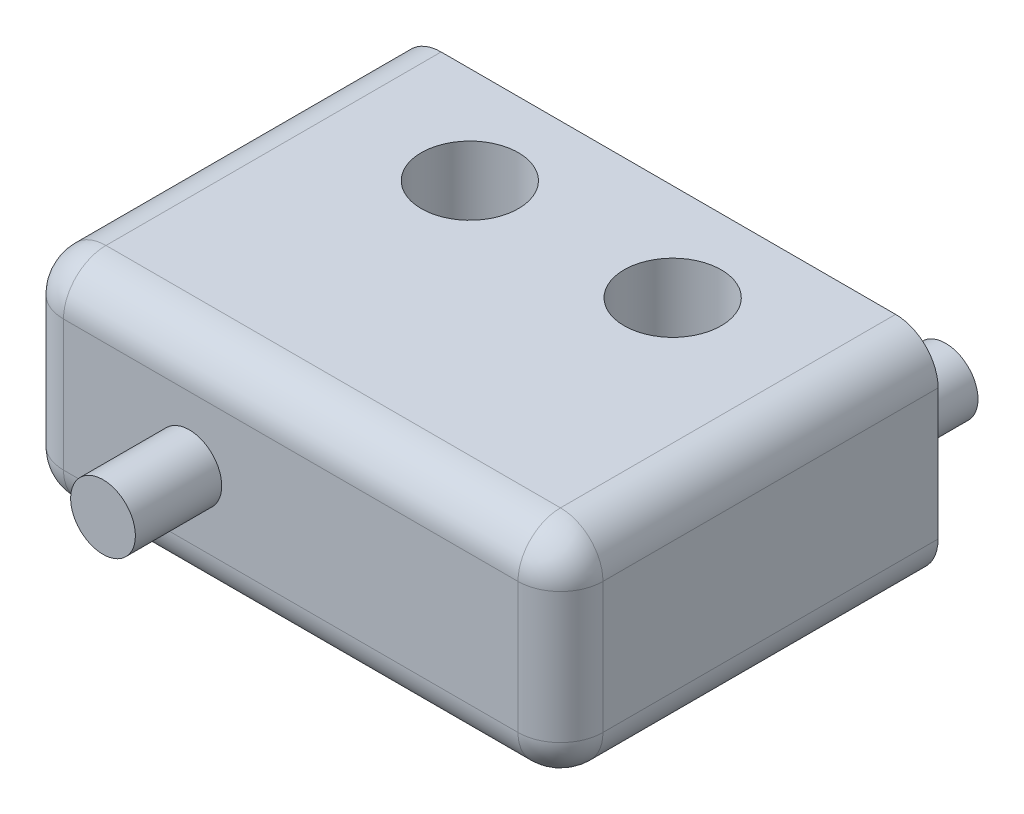
SolidWorks part; units mm, degrees
material "Калифорния"
ref_plane "Front" through (0, 0, 0) normal (0, 0, 1) x (1, 0, 0)
ref_plane "Top" through (0, 0, 0) normal (0, 1, 0) x (1, 0, 0)
ref_plane "Right" through (0, 0, 0) normal (1, 0, 0) x (0, 0, -1)
sketch "Эскиз1" plane through (0, 0, 0) normal (0, 0, 1) x (1, 0, 0)
  line L1 (-6.35, 2.54) -> (6.35, 2.54)
  line L2 (-6.35, 2.54) -> (-6.35, -2.54)
  line L3 (-6.35, -2.54) -> (6.35, -2.54)
  line L4 (6.35, 2.54) -> (6.35, -2.54)
  line L5 (-6.35, 2.54) -> (6.35, -2.54) construction
  line L6 (-6.35, -2.54) -> (6.35, 2.54) construction
  point P0 (0, 0)
  dimension "D1" = 12.7
  dimension "D2" = 5.08
extrude "Бобышка-Вытянуть1" add sketch "Эскиз1" along normal blind 8.89
sketch "Эскиз2" plane through (0, 0, 0) normal (0, 0, -1) x (-1, 0, 0)
  line L0 (6.35, 2.54) -> (6.35, -2.54) construction
  line L1 (-6.35, 2.54) -> (6.35, 2.54) construction
  circle A0 centre (-4.7498, 0) radius 0.762
  circle A1 centre (0, 0) radius 0.762
  circle A2 centre (4.7498, 0) radius 0.762
  dimension "D1" = 4.7498
  dimension "D2" = 4.7498
  dimension "D3" = 1.6002
  dimension "D4" = 2.54
  dimension "D5" = 2.54
  dimension "D6" = 2.54
extrude "Бобышка-Вытянуть2" add sketch "Эскиз2" along normal blind 1.778
sketch "Эскиз3" plane through (0, 0, 8.89) normal (0, 0, 1) x (1, 0, 0)
  line L0 (-6.35, -2.54) -> (6.35, -2.54) construction
  circle A0 centre (-2.3876, 0) radius 0.762
  dimension "D1" = 2.3876
  dimension "D2" = 2.54
extrude "Бобышка-Вытянуть3" add sketch "Эскиз3" along normal blind 2.032
fillet "Скругление2" radius 1 4 edges at (-6.35, 0, 8.89) (0, -2.54, 8.89) (6.35, 0, 8.89) (0, 2.54, 8.89)
fillet "Скругление3" radius 1 8 edges at (-6.0571, -2.2471, 8.5971) (-6.0571, 2.2471, 8.5971) (6.0571, 2.2471, 8.5971) (6.0571, -2.2471, 8.5971) (-6.35, -2.54, 3.945) (-6.35, 2.54, 3.945) (6.35, 2.54, 3.945) (6.35, -2.54, 3.945)
sketch "Эскиз4" plane through (0, 2.54, 0) normal (0, 1, 0) x (1, 0, 0)
  line L0 (5.35, 0) -> (-5.35, 0) construction
  line L1 (-6.35, -7.89) -> (-6.35, 0) construction
  circle A0 centre (-2.3876, -2.286) radius 1.143
  circle A1 centre (2.3876, -2.286) radius 1.143
  dimension "D1" = 2.286
  dimension "D2" = 2.286
  dimension "D3" = 4.7752
  dimension "D4" = 3.9624
extrude "Вырез-Вытянуть1" cut sketch "Эскиз4" against normal blind 6
